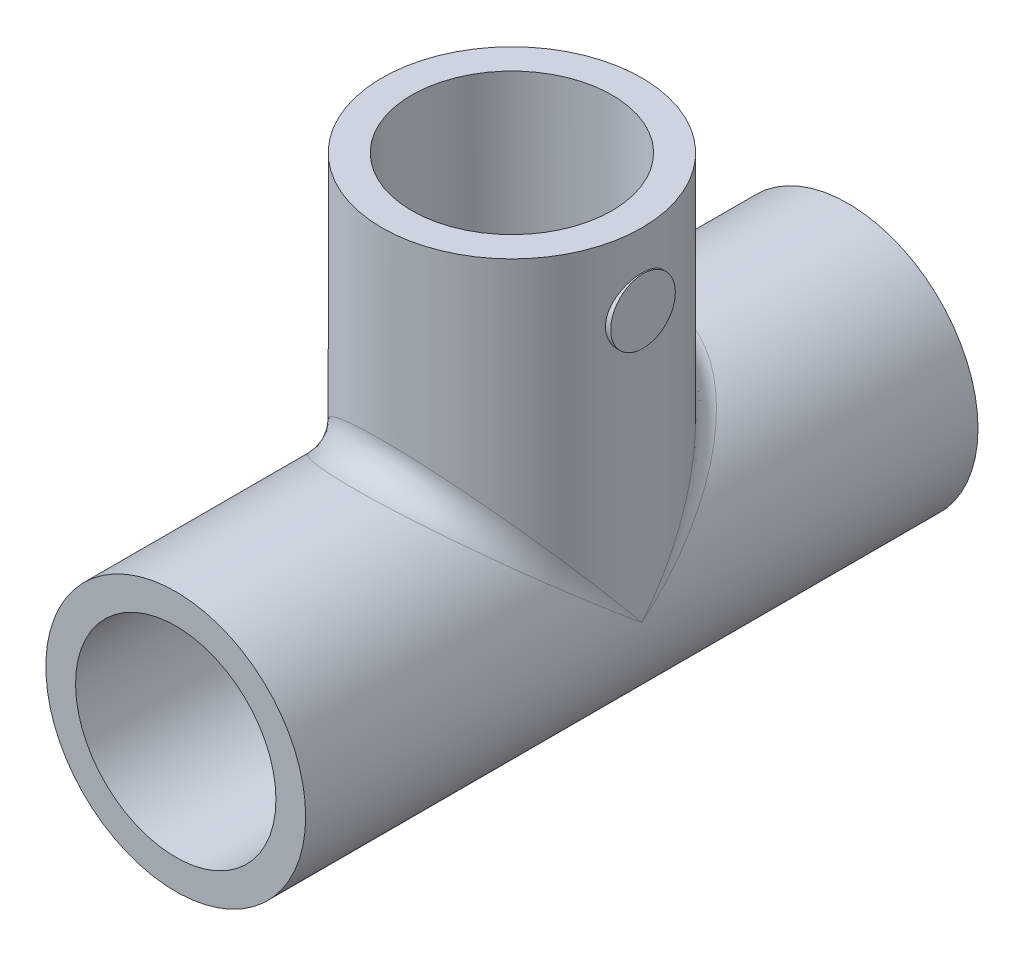
SolidWorks part; units mm, degrees
material "PVC Rígido"
ref_plane "Alzado" through (0, 0, 0) normal (0, 0, 1) x (1, 0, 0)
ref_plane "Planta" through (0, 0, 0) normal (0, 1, 0) x (1, 0, 0)
ref_plane "Vista lateral" through (0, 0, 0) normal (1, 0, 0) x (0, 0, -1)
sketch "Croquis1" plane through (0, 0, 0) normal (0, 0, 1) x (1, 0, 0)
  circle A0 centre (0, 0) radius 13.875
  circle A1 centre (0, 0) radius 10.7
  dimension "D1" = 27.75
  dimension "D2" = 21.4
extrude "Saliente-Extruir1" add sketch "Croquis1" along normal mid plane 71.8
sketch "Croquis2" plane through (0, 0, 0) normal (0, 1, 0) x (1, 0, 0)
  circle A0 centre (0, 0) radius 13.875
  circle A1 centre (0, 0) radius 10.7
  dimension "D1" = 21.4
extrude "Saliente-Extruir2" add sketch "Croquis2" along normal blind 36.5
sketch "Croquis6" plane through (0, 0, 0) normal (0, 0, 1) x (1, 0, 0)
  circle A0 centre (0, 0) radius 9.5
  circle A1 centre (0, 0) radius 10.7
  circle A2 centre (0, 0) radius 10.7 construction
  dimension "D1" = 19
extrude "Saliente-Extruir4" add sketch "Croquis6" along normal mid plane 27
sketch "Croquis3" plane through (0, 0, 35.9) normal (0, 0, 1) x (1, 0, 0)
  circle A0 centre (0, 0) radius 9.5
  arc A2 (-3.204, 8.9434) -> (3.204, 8.9434) centre (0, 0) ccw construction
extrude "Cortar-Extruir1" cut sketch "Croquis3" against normal through all
sketch "Croquis4" plane through (0, 36.5, 0) normal (0, 1, 0) x (1, 0, 0)
  circle A0 centre (0, 0) radius 10.7
  circle A1 centre (0, 0) radius 10.7 construction
extrude "Cortar-Extruir2" cut sketch "Croquis4" against normal blind 37.5
fillet "Redondeo1" radius 3 2 edges at (0, 13.875, -13.875) (0, 13.875, 13.875)
sketch "Croquis7" plane through (0, 0, 0) normal (1, 0, 0) x (0, 0, -1)
  circle A0 centre (0, 28.8698) radius 3.4512
extrude "Saliente-Extruir5" add sketch "Croquis7" against normal up to next from offset 14
